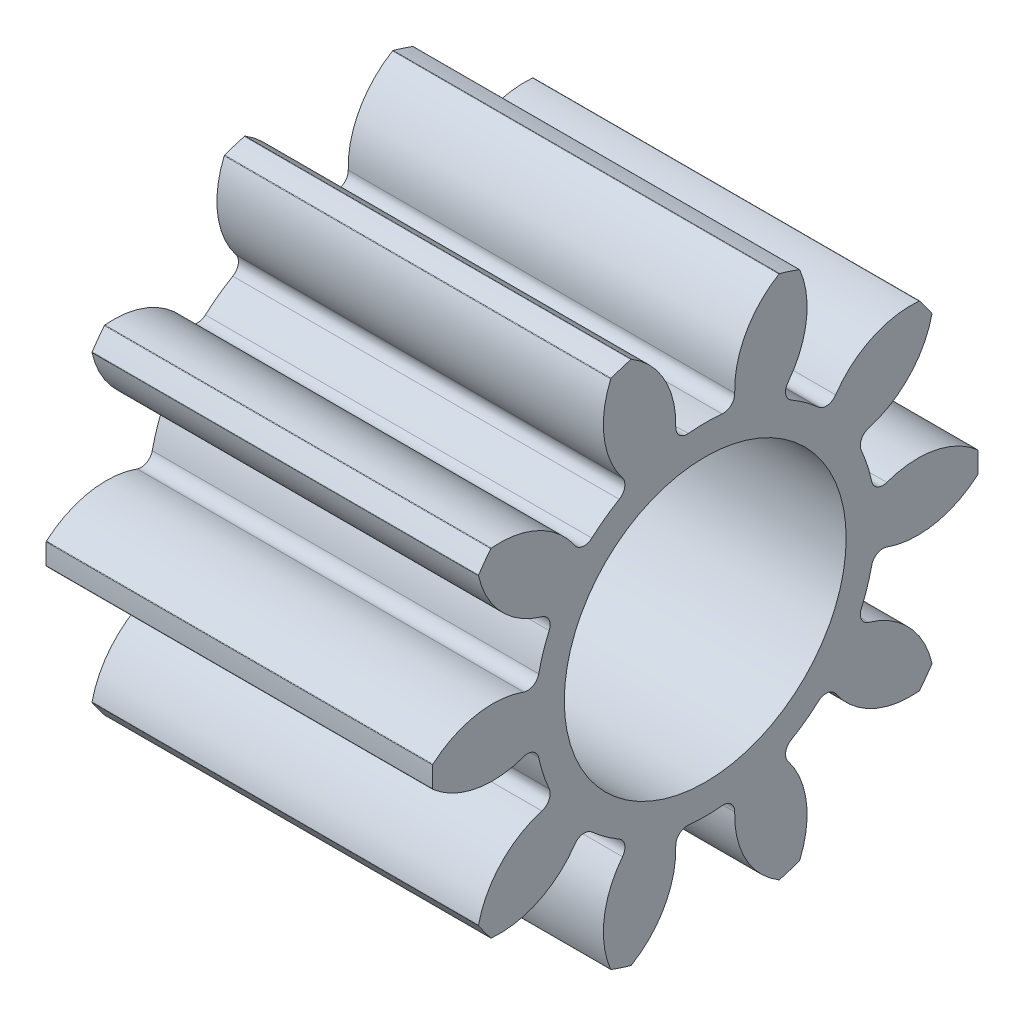
SolidWorks part; units mm, degrees
ref_plane "Plane1" through (0, 0, 0) normal (0, 0, 1) x (1, 0, 0)
ref_plane "Plane2" through (0, 0, 0) normal (0, 1, 0) x (1, 0, 0)
ref_plane "Plane3" through (0, 0, 0) normal (1, 0, 0) x (0, 0, -1)
sketch "HoldingSke" plane through (0, 0, 0) normal (0, 1, 0) x (1, 0, 0)
  line L0 (0, 0) -> (0.9848, -0.1736)
  line L1 (-15, 0) -> (100, 0) construction
  line L2 (0, 0) -> (-2.1039, 2.3779)
  line L3 (0, 0) -> (-11.863, 4.5341)
  line L4 (0, 0) -> (8.5048, 1.4996)
  line L5 (0, 0) -> (-46.8476, -17.4728)
  line L6 (0, 0) -> (-8.2896, -5.593)
  line L7 (-2.1039, 2.3779) -> (8.6586, 51.2059)
  line L8 (-76.2, 54.61) -> (-75.7, 54.61)
  line L9 (-67.7845, 28.3722) -> (-49.3413, 33.142)
  line L10 (-76.2, 71.12) -> (104.1128, 71.12)
  line L11 (0, 0) -> (-10, 0)
  line L12 (-76.2, 101.6) -> (-76.162, 101.6)
  line L13 (24.9733, 27.94) -> (52.9518, 28.4284)
  line L14 (24.9733, 27.94) -> (24.9743, 27.94)
  line L15 (24.9733, 27.94) -> (100.4006, 29.5858)
  line L16 (-63.627, -1) -> (-12.827, -1)
  circle A0 centre (0, 0) radius 1.5
  circle A1 centre (0, 0) radius 3.749
  circle A2 centre (0, 0) radius 37.5
  circle A3 centre (0, 0) radius 1.5
  dimension "Num_teeth" = 10
  dimension "Pitch_radius" = 180.3128
  dimension "Width" = 10
sketch "BasProSke" plane through (0, 0, 0) normal (0, 1, 0) x (1, 0, 0)
  line L0 (-10, 0) -> (60, 0) construction
  line L1 (0, 0) -> (0, 6)
  line L2 (0, 0) -> (8.5, 0)
  line L3 (8.5, 0) -> (8.5, 6)
  line L4 (8.5, 6) -> (0, 6)
  dimension "Thickness" = 8.5
  dimension "Diameter" = 12
revolve "Base-Revolve" add sketch "BasProSke" angle 360 about L0
sketch "TooCutSke" plane through (0, 0, 0) normal (1, 0, 0) x (0, 0, -1)
  line L1 (0, 0) -> (0, 107) construction
  line L2 (0, 0) -> (-0.8485, 4.9275) construction
  line L3 (0, 0) -> (-3.0584, 9.4126) construction
  line L4 (-0.8485, 4.9275) -> (-1.5292, 4.7063) construction
  arc A0 (0.6809, 3.6866) -> (-0.6809, 3.6866) centre (0, 0) ccw
  arc A1 (1.66, 5.7922) -> (-1.66, 5.7922) centre (0, 0) ccw
  circle A2 centre (0, 0) radius 5 construction
  circle A3 centre (0, 0) radius 4.8407 construction
  arc A4 (-0.6809, 3.6866) -> (-1.66, 5.7922) centre (-2.6471, 4.0528) ccw
  arc A5 (1.66, 5.7922) -> (0.6809, 3.6866) centre (2.6471, 4.0528) ccw
extrude "ToothCut" cut sketch "TooCutSke" along normal through all
fillet "Breaks" radius 0.02 2 edges at (4.25, 5.7745, -1.6294) (4.25, 5.7745, 1.6294) tangent propagation no
fillet "RootFillets" radius 0.251 2 edges at (4.25, 3.6866, -0.6809) (4.25, 3.6866, 0.6809)
pattern_circular "TeethCuts" count 10 every 36 about axis through (-10, 0, 0) along (1, 0, 0) of "ToothCut", "RootFillets", "Breaks"
sketch "HubNeaOneSke" plane through (0, 0, 0) normal (-1, 0, 0) x (0, 0, 1)
  circle A0 centre (0, 0) radius 3.749
  dimension "Diameter" = 7.498
extrude "HubNearOne" [suppressed] add sketch "HubNeaOneSke" along normal blind 41.5001
sketch "HubNeaBotSke" plane through (0, 0, 0) normal (-1, 0, 0) x (0, 0, 1)
  circle A0 centre (0, 0) radius 3.749
  dimension "Diameter" = 7.498
extrude "HubNearBoth" [suppressed] add sketch "HubNeaBotSke" along normal blind 20.75
ref_plane "FarPln" through (8.5, 0, 0) normal (1, 0, 0) x (0, 0, -1)
sketch "HubFarSke" plane through (8.5, 0, 0) normal (1, 0, 0) x (0, 0, -1)
  circle A0 centre (0, 0) radius 3.749
  dimension "Diameter" = 7.498
extrude "HubFar" [suppressed] add sketch "HubFarSke" along normal blind 20.75
sketch "BorSke" plane through (0, 0, 0) normal (1, 0, 0) x (0, 0, -1)
  circle A0 centre (0, 0) radius 1.8
  dimension "Diameter" = 3.6
extrude "Bore" cut sketch "BorSke" along normal mid plane 100.0001
sketch "KeySke" plane through (0, 0, 0) normal (1, 0, 0) x (0, 0, -1)
  line L0 (-0.6, 0) -> (-0.6, 2)
  line L1 (-0.6, 2) -> (0.6, 2)
  line L2 (0.6, 2) -> (0.6, 0)
  line L3 (0, 0) -> (0, 34) construction
  line L4 (-0.6, 0) -> (0.6, 0)
  dimension "Width" = 1.2
extrude "Keyway" [suppressed] cut sketch "KeySke" along normal mid plane 100.0001
pattern_circular "Keyway2" [suppressed] count 2 every 90 about axis through (-10, 0, 0) along (1, 0, 0) reverse direction yes
sketch "Sketch3" plane through (0, 0, 0) normal (-1, 0, 0) x (0, 0, 1)
  circle A0 centre (0, 0) radius 2.5
  circle A1 centre (0, 0) radius 1.8 construction
  circle A2 centre (0, 0) radius 1.8
  dimension "D1" = 5
extrude "Boss-Extrude1" add sketch "Sketch3" along normal blind 1
sketch "Sketch4" plane through (8.5, 0, 0) normal (1, 0, 0) x (0, 0, -1)
  circle A0 centre (0, 0) radius 3.1
  dimension "D1" = 6.2
extrude "Cut-Extrude2" cut sketch "Sketch4" against normal blind 5
chamfer "Chamfer2" distance 0.5 angle 45 1 edges at (-1, 0, 2.5)
equation "' \"Module@HoldingSke\" = 6.35"
equation "' \"Num_teeth@HoldingSke\" = 12"
equation "' \"Ap@HoldingSke\" =  20"
equation "' \"Ap@HoldingSke\" = 20"
equation "' \"Width@HoldingSke\" = 0.5 * 25.4"
equation "' \"Hub_dia@HoldingSke\"= 1 * 25.4"
equation "' \"Hub_dia@HoldingSke\" = 1 * 25.4"
equation "' \"Overall_len@HoldingSke\" = 1.0 * 25.4"
equation "' \"Bore@HoldingSke\" = 0.75 * 25.4"
equation "' \"T_dim@HoldingSke\" = 0.1 * 25.4"
equation "' \"Width@KeySke\" = 0.25 * 25.4"
equation "' \"Show_teeth@HoldingSke\" = 13"
equation "' \"Backlash@HoldingSke\" = 0.009 * 25.4"
equation "' \"Addendum_fac@HoldingSke\" = 1.0"
equation "' \"Dedendum_fac@HoldingSke\" = 1.25"
equation "' \"Dedendum_add@HoldingSke\" = 0.00005 * 25.4"
equation "' \"Clearance_fac@HoldingSke\" = 0.25"
equation "\"Pitch@HoldingSke\" = 1 / \"Module@HoldingSke\""
equation "\"Overcut_dia@TooCutSke\" = (\"Num_teeth@HoldingSke\" + 2 * \"Addendum_fac@HoldingSke\") / \"Pitch@HoldingSke\" + 0.002 * 25.4"
equation "\"Pitch_dia@TooCutSke\" = \"Num_teeth@HoldingSke\" / \"Pitch@HoldingSke\""
equation "\"Base_dia@TooCutSke\" = \"Num_teeth@HoldingSke\" / \"Pitch@HoldingSke\" * cos((\"Ap@HoldingSke\"  * 3.14159265 / 180))"
equation "\"Root_dia@TooCutSke\" = (\"Num_teeth@HoldingSke\" + 2) / \"Pitch@HoldingSke\" - 2 * (\"Addendum_fac@HoldingSke\" + \"Dedendum_fac@HoldingSke\") / \"Pitch@HoldingSke\" - \"Dedendum_add@HoldingSke\" * 2"
equation "\"Half_ang@TooCutSke\" = 180 / \"Num_teeth@HoldingSke\""
equation "\"Half_CT@TooCutSke\" = \"Num_teeth@HoldingSke\" / \"Pitch@HoldingSke\" * sin((3.14159265 / 2 / \"Num_teeth@HoldingSke\")) / 2 - 7 * \"Backlash@HoldingSke\" / 4"
equation "\"Flank_rad@TooCutSke\" = \"Num_teeth@HoldingSke\" / \"Pitch@HoldingSke\" / 5"
equation "\"Radius@RootFillets\" = \"Clearance_fac@HoldingSke\" / \"Pitch@HoldingSke\" + \"Dedendum_add@HoldingSke\""
equation "\"Break_rad@Breaks\" = 0.02 / \"Pitch@HoldingSke\""
equation "\"Thickness@HoldingSke\" = \"Width@HoldingSke\""
equation "\"OAL@HoldingSke\" = \"Thickness@HoldingSke\""
equation "\"MHD@HoldingSke\" = (\"Num_teeth@HoldingSke\" + 2) / \"Pitch@HoldingSke\" - 2 * (\"Addendum_fac@HoldingSke\" + \"Dedendum_fac@HoldingSke\")  / \"Pitch@HoldingSke\" - \"Dedendum_add@HoldingSke\" * 2"
equation "\"MBD@HoldingSke\" = (\"Num_teeth@HoldingSke\" + 2) / \"Pitch@HoldingSke\" - 2 * (\"Addendum_fac@HoldingSke\" + \"Dedendum_fac@HoldingSke\")  / \"Pitch@HoldingSke\" - \"Dedendum_add@HoldingSke\" * 2 - 0.002 * 25.4"
equation "\"MHD@HoldingSke\" = ((sgn( \"MHD@HoldingSke\" - \"Hub_dia@HoldingSke\" )-1)*( \"MHD@HoldingSke\" - \"Hub_dia@HoldingSke\" ))/-2+ \"Hub_dia@HoldingSke\""
equation "\"MBD@HoldingSke\" = ((sgn( \"MBD@HoldingSke\" - \"Bore@HoldingSke\" )-1)*( \"MBD@HoldingSke\" - \"Bore@HoldingSke\" ))/-2+ \"Bore@HoldingSke\""
equation "\"OAL@HoldingSke\" = ((sgn( \"OAL@HoldingSke\" - \"Overall_len@HoldingSke\" )+1)*( \"OAL@HoldingSke\" - \"Overall_len@HoldingSke\" ))/2 + \"Overall_len@HoldingSke\" + 0.000002 * 25.4"
equation "\"Num_teeth@TeethCuts\" = int( \"Show_teeth@HoldingSke\" ) + 1"
equation "\"Num_teeth@TeethCuts\" = ((sgn( \"Num_teeth@TeethCuts\" - \"Num_teeth@HoldingSke\" )-1)*( \"Num_teeth@TeethCuts\" - \"Num_teeth@HoldingSke\" ))/-2+ \"Num_teeth@HoldingSke\""
equation "\"Num_teeth@TeethCuts\" = ((sgn( \"Num_teeth@TeethCuts\" - 2.0)+1)*( \"Num_teeth@TeethCuts\" - 2.0))/2 +2.0"
equation "\"Angle@TeethCuts\" = 360.0 / \"Num_teeth@HoldingSke\""
equation "\"Diameter@BasProSke\" = (\"Num_teeth@HoldingSke\" + 2 * \"Addendum_fac@HoldingSke\") / \"Pitch@HoldingSke\""
equation "' \"Fillet_rad@BasProSke\" =  \"Thickness@HoldingSke\" * 0.05"
equation "' \"Fillet_rad@BasProSke\" = \"Thickness@HoldingSke\" * 0.05"
equation "\"MHD@HoldingSke\" = ((sgn( \"MHD@HoldingSke\" - \"Root_dia@TooCutSke\" )-1)*( \"MHD@HoldingSke\" - \"Root_dia@TooCutSke\" ))/-2+ \"Root_dia@TooCutSke\""
equation "\"Diameter@HubNeaOneSke\" = \"MHD@HoldingSke\""
equation "\"Length@HubNearOne\" = \"OAL@HoldingSke\" - \"Thickness@BasProSke\""
equation "\"Diameter@HubNeaBotSke\" = \"MHD@HoldingSke\""
equation "\"Length@HubNearBoth\" = ( \"OAL@HoldingSke\" - \"Thickness@BasProSke\" ) / 2.0"
equation "\"Thickness@FarPln\" = \"Thickness@BasProSke\""
equation "\"Diameter@HubFarSke\" = \"MHD@HoldingSke\""
equation "\"Length@HubFar\" = ( \"OAL@HoldingSke\" - \"Thickness@BasProSke\" ) / 2.0"
equation "\"D1@Bore\" = \"OAL@HoldingSke\" * 2.0"
equation "\"D1@Keyway\" = \"OAL@HoldingSke\" * 2.0"
equation "\"Offset@KeySke\" = \"T_dim@HoldingSke\" + \"MBD@HoldingSke\" / 2.0"
